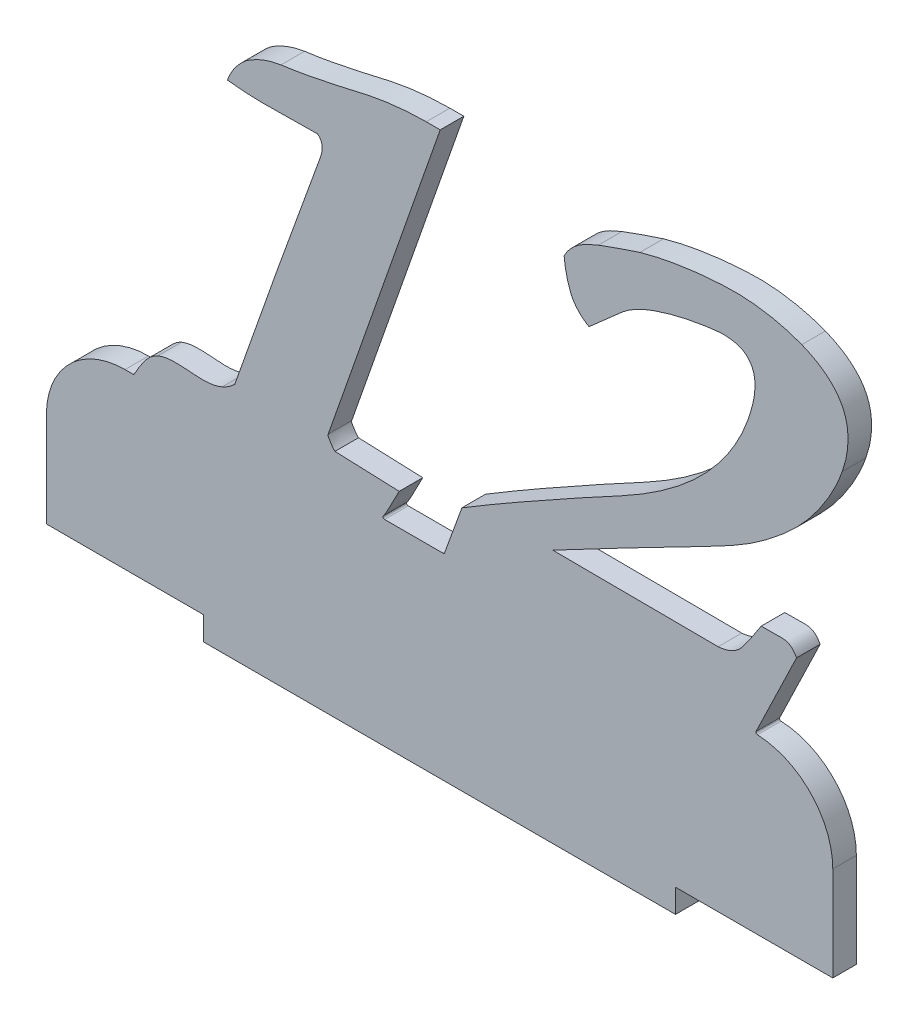
SolidWorks part; units mm, degrees
ref_plane "Front Plane" through (0, 0, 0) normal (0, 0, 1) x (1, 0, 0)
ref_plane "Top Plane" through (0, 0, 0) normal (0, 1, 0) x (1, 0, 0)
ref_plane "Right Plane" through (0, 0, 0) normal (1, 0, 0) x (0, 0, -1)
sketch "Sketch1" plane through (0, 0, 0) normal (0, 0, 1) x (1, 0, 0)
  line L0 (0, 20) -> (100, 20) construction
  line L1 (42.538, 22) -> (50.5846, 22)
  line L2 (0, 22) -> (0, 0)
  line L3 (0, 0) -> (20, 0)
  line L4 (100, 22) -> (100, 0)
  line L5 (0, 22) -> (11.1263, 22)
  line L6 (90.1102, 22) -> (100, 22)
  line L7 (50.0836, 68.4434) -> (35.8342, 27.8062)
  line L8 (36.6942, 26.3402) -> (44.8647, 26.0274)
  line L9 (95.3924, 32.9469) -> (90.1102, 22)
  line L11 (80, 0) -> (100, 0)
  line L12 (50.5846, 22) -> (52.8396, 28.1971)
  line L13 (20, 0) -> (20, -3)
  line L14 (20, -3) -> (80, -3)
  line L15 (80, 0) -> (80, -3)
  line L16 (73.2853, 59.9993) -> (69.0046, 56.2268)
  line L17 (64.3916, 29.3113) -> (85.4237, 29.194)
  spline S0 degree 3 poles (44.8647, 26.0274) (44.2697, 25.0142) (43.7246, 23.692) (42.9044, 22.3528) (42.6284, 22.0797) (42.538, 22) knots 0 0 0 0 0.504343 0.619768 0.671675 0.671675 0.671675 0.671675
  spline S1 degree 3 poles (11.1263, 22) (11.1792, 22.0913) (11.4793, 22.616) (12.2608, 24.0179) (13.2554, 25.1875) (14.1962, 25.617) knots 0.196061 0.196061 0.196061 0.196061 0.248912 0.498933 1 1 1 1
  spline S2 degree 3 poles (14.1962, 25.617) (15.5375, 26.1362) (18.2883, 25.8615) (21.0576, 25.7058) (22.3666, 26.2816) knots 0 0 0 0 0.501452 1 1 1 1
  spline S3 degree 2 poles (22.3666, 26.2816) (23.2482, 26.6721) (23.9499, 27.3371) knots 0 0 0 1 1 1
  spline S4 degree 3 poles (23.9499, 27.3371) (25.7322, 32.3722) (29.2572, 42.495) (32.9462, 52.5592) (34.7787, 57.6146) knots 0 0 0 0 0.498323 1 1 1 1
  spline S5 degree 3 poles (34.7787, 57.6146) (34.9618, 58.1122) (35.257, 59.0787) (34.8044, 59.9901) (34.4464, 60.1948) knots 0 0 0 0 0.581397 1 1 1 1
  spline S6 degree 3 poles (34.4464, 60.1948) (32.5297, 60.2286) (28.7247, 60.0447) (24.9117, 60.1494) (23.0312, 60.3902) knots 0 0 0 0 0.503015 1 1 1 1
  spline S7 degree 3 poles (23.0312, 60.3902) (23.2632, 61.0574) (23.7474, 62.0064) (24.6654, 63.0671) (25.4387, 63.7896) (26.3867, 64.3433) (27.8137, 65.026) (29.0057, 65.3408) (29.8334, 65.4723) knots 0 0 0 0 0.237267 0.352024 0.469659 0.590381 0.718477 1 1 1 1
  spline S8 degree 3 poles (29.8334, 65.4723) (32.9457, 65.8708) (36.8074, 66.7228) (41.4292, 67.8026) (44.5091, 68.2851) (46.8022, 68.4326) (48.3049, 68.4434) knots 0 0 0 0 0.501478 0.63281 0.759518 1 1 1 1
  spline S9 degree 3 poles (48.3049, 68.4434) (48.5134, 68.4434) (49.1063, 68.4434) (49.6992, 68.4434) (50.0836, 68.4434) knots 0 0 0 0 0.351648 1 1 1 1
  spline S10 degree 3 poles (35.8342, 27.8062) (35.781, 27.6064) (36.1126, 27.0967) (36.3903, 26.6139) (36.6942, 26.3402) knots 0 0 0 0 0.324502 1 1 1 1
  spline S11 degree 3 poles (52.8396, 28.1971) (54.2487, 29.0455) (56.4319, 30.3574) (59.4743, 32.0901) (61.9449, 33.5248) (64.5708, 34.9857) (67.3363, 36.5114) (70.2313, 38.1215) (73.255, 39.7104) (76.2, 41.3977) (78.9066, 43.2251) (81.348, 45.1126) (83.4906, 47.1182) (85.3574, 49.2063) (87.4282, 52.0813) (88.6308, 54.4095) (89.1962, 56.0314) knots 0 0 0 0 0.105525 0.163386 0.224617 0.288806 0.356162 0.427253 0.501314 0.575301 0.644862 0.710669 0.773069 0.83288 0.890073 1 1 1 1
  spline S12 degree 3 poles (89.1962, 56.0314) (89.6258, 57.2668) (90.1551, 59.0155) (90.1058, 61.2374) (89.6665, 62.4393) (88.8489, 63.339) (87.6356, 63.8109) (86.1365, 63.9921) (84.3963, 63.8036) (82.5783, 63.4938) (80.8129, 63.1549) (79.2044, 62.7382) (77.7367, 62.2898) (76.4026, 61.8142) (74.8969, 61.1028) (73.8661, 60.4961) (73.2853, 59.9993) knots 0 0 0 0 0.163534 0.223587 0.273098 0.319543 0.36998 0.431294 0.506061 0.586527 0.660902 0.729495 0.793065 0.851774 0.905429 1 1 1 1
  spline S13 degree 3 poles (69.0046, 56.2268) (68.4737, 56.5267) (67.548, 57.252) (66.902, 58.2352) (66.6981, 58.7483) knots 0 0 0 0 0.525688 1 1 1 1
  spline S14 degree 2 poles (66.6981, 58.7483) (65.989, 60.5294) (65.8381, 62.4426) knots 0 0 0 1 1 1
  spline S15 degree 3 poles (65.8381, 62.4426) (66.2166, 63.2045) (67.4829, 64.6614) (69.2487, 65.4253) (70.197, 65.8046) knots 0 0 0 0 0.45102 1 1 1 1
  spline S16 degree 2 poles (70.197, 65.8046) (72.817, 66.777) (75.4745, 67.642) knots 0 0 0 1 1 1
  spline S17 degree 3 poles (75.4745, 67.642) (77.0977, 68.1095) (79.6167, 68.6285) (83.0638, 69.0975) (85.7514, 69.3062) (88.4527, 69.3817) (91.9385, 69.0272) (94.4655, 68.4058) (96.057, 67.7788) knots 0 0 0 0 0.24204 0.368376 0.498665 0.628562 0.755291 1 1 1 1
  spline S18 degree 3 poles (96.057, 67.7788) (97.2343, 67.3003) (98.8825, 66.4239) (100.5441, 64.7297) (101.3968, 63.3512) (101.8684, 61.7975) (102.0456, 59.4144) (101.6295, 57.5771) (101.1977, 56.3636) knots 0 0 0 0 0.269969 0.386879 0.498158 0.609266 0.726759 1 1 1 1
  spline S19 degree 3 poles (101.1977, 56.3636) (100.6279, 54.7052) (99.4018, 52.3442) (97.3301, 49.4325) (95.4784, 47.3457) (93.3295, 45.4009) (90.939, 43.5347) (88.2704, 41.7904) (84.3974, 39.7053) (79.5877, 37.282) (72.6041, 33.6246) (67.5743, 31.0236) (64.3916, 29.3113) knots 0 0 0 0 0.112096 0.169586 0.228764 0.29055 0.355137 0.423026 0.494633 0.636984 0.76832 1 1 1 1
  spline S20 degree 3 poles (85.4237, 29.194) (86.0826, 29.2521) (87.0565, 29.4765) (88.111, 30.2214) (89.3445, 31.7084) (90.1323, 33.1285) (90.8967, 34.1979) knots 0 0 0 0 0.257232 0.374596 0.49231 1 1 1 1
  spline S21 degree 3 poles (90.8967, 34.1979) (91.7487, 34.1596) (92.7865, 34.2465) (94.0411, 34.1996) (94.8108, 33.8488) (95.1965, 33.3225) (95.3924, 32.9469) knots 0 0 0 0 0.506825 0.628241 0.743426 1 1 1 1
  dimension "D1" = 100
  dimension "D2" = 3
  dimension "D3" = 20
  dimension "D4" = 20
  dimension "D5" = 20
extrude "Boss-Extrude1" add sketch "Sketch1" along normal blind 3
fillet "Fillet1" radius 10 2 edges at (0, 22, 1.5) (100, 22, 1.5)
fillet "Fillet2" radius 0.2 4 edges at (90.1102, 22, 1.5) (42.538, 22, 1.5) (50.5846, 22, 1.5) (11.1263, 22, 1.5)
